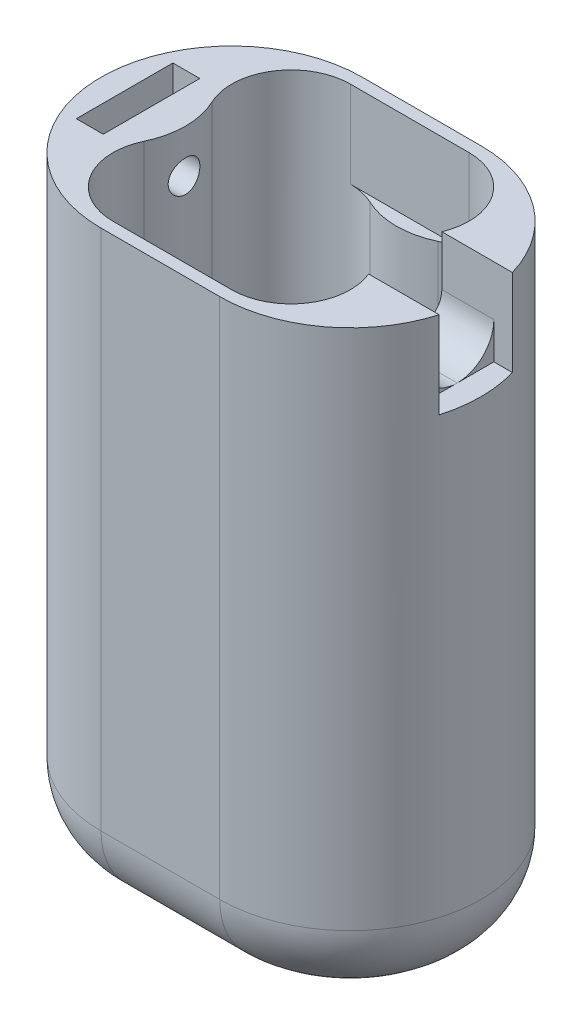
SolidWorks part; units mm, degrees
ref_plane "Front Plane" through (0, 0, 0) normal (0, 0, 1) x (1, 0, 0)
ref_plane "Top Plane" through (0, 0, 0) normal (0, 1, 0) x (1, 0, 0)
ref_plane "Right Plane" through (0, 0, 0) normal (1, 0, 0) x (0, 0, -1)
sketch "Sketch1" plane through (0, 0, 0) normal (0, 1, 0) x (1, 0, 0)
  line L0 (0, 0) -> (-23.105, 0) construction
  line L1 (-7.5, 0) -> (7.5, 0) construction
  line L2 (0, 13.7042) -> (0, -14.0987) construction
  line L3 (-7.5, 16.5) -> (7.5, 16.5)
  line L4 (-7.5, -16.5) -> (7.5, -16.5)
  line L5 (-7.5, 15) -> (-7.5, 16.5) construction
  arc A0 (-4.2857, 14.2763) -> (-14.2763, 4.2857) centre (-7.5, 7.5) ccw
  arc A1 (4.2857, 14.2763) -> (14.2763, 4.2857) centre (7.5, 7.5) cw
  arc A2 (4.2857, -14.2763) -> (14.2763, -4.2857) centre (7.5, -7.5) ccw
  arc A3 (-4.2857, -14.2763) -> (-14.2763, -4.2857) centre (-7.5, -7.5) cw
  arc A4 (14.2763, -4.2857) -> (14.2763, 4.2857) centre (23.3114, 0) cw
  arc A5 (-4.2857, -14.2763) -> (4.2857, -14.2763) centre (0, -23.3114) cw
  arc A6 (-14.2763, 4.2857) -> (-14.2763, -4.2857) centre (-23.3114, 0) cw
  arc A7 (-4.2857, 14.2763) -> (4.2857, 14.2763) centre (0, 23.3114) ccw
  arc A8 (-7.5, 16.5) -> (-7.5, -16.5) centre (-7.5, 0) ccw
  arc A9 (7.5, -16.5) -> (7.5, 16.5) centre (7.5, 0) ccw
  point P5 (0, 0)
  point P16 (7.5, 0)
  point P19 (0, -7.5)
  point P22 (-7.5, 0)
  point P25 (0, 7.5)
  point P32 (-7.5, 16.992)
  point P33 (-7.5, 15)
  point P36 (-8.7147, 14.901)
  point P37 (-7.5, 17.0404)
  dimension "D1" = 15
  dimension "D2" = 10
  dimension "D3" = 1.5
extrude "Boss-Extrude1" add sketch "Sketch1" along normal blind 55
sketch "Sketch2" plane through (0, 0, 0) normal (0, -1, 0) x (1, 0, 0)
  line L0 (-7.5, 0) -> (7.5, 0) construction
  line L1 (-7.5, 16.5) -> (7.5, 16.5)
  line L2 (-7.5, -16.5) -> (7.5, -16.5)
  line L3 (7.5, -16.5) -> (-7.5, -16.5) construction
  arc A0 (-7.5, 16.5) -> (-7.5, -16.5) centre (-7.5, 0) ccw
  arc A1 (7.5, -16.5) -> (7.5, 16.5) centre (7.5, 0) ccw
  arc A2 (-7.5, 16.5) -> (-7.5, -16.5) centre (-7.5, 0) ccw construction
  point P3 (0, 0)
extrude "Boss-Extrude2" add sketch "Sketch2" along normal blind 10
fillet "Fillet1" radius 10 4 edges at (24, -10, 0) (0, -10, -16.5) (-24, -10, 0) (0, -10, 16.5)
sketch "Sketch4" plane through (0, 55, 0) normal (0, 1, 0) x (1, 0, 0)
  line L0 (-7.5, -16.5) -> (7.5, -16.5) construction
  line L1 (-7.5, 16.5) -> (7.5, 16.5)
  line L2 (-7.5, -16.5) -> (7.5, -16.5)
  line L3 (24, 0) -> (24, 4.625) construction
  line L4 (14.4271, 4.625) -> (23.3385, 4.625)
  line L5 (7.5, 16.5) -> (-7.5, 16.5) construction
  line L6 (14.4271, -4.625) -> (23.3385, -4.625)
  line L7 (-7.5, 15) -> (7.5, 15)
  line L8 (-24, 0) -> (-21.0182, 0) construction
  line L9 (24, 0) -> (24, -4.625) construction
  line L10 (7.5, -15) -> (-7.5, -15)
  line L12 (-17.6182, 0) -> (-13.3114, 0) construction
  line L15 (-21.0182, 6.1) -> (-17.6182, 6.1)
  line L16 (-21.0182, 6.1) -> (-21.0182, -6.1)
  line L17 (-21.0182, -6.1) -> (-17.6182, -6.1)
  line L18 (-17.6182, 6.1) -> (-17.6182, -6.1)
  arc A0 (-7.5, 16.5) -> (-7.5, -16.5) centre (-7.5, 0) ccw construction
  arc A1 (7.5, -16.5) -> (23.3385, -4.625) centre (7.5, 0) ccw
  arc A3 (7.5, -15) -> (14.4271, -4.625) centre (7.5, -7.5) ccw
  arc A4 (-4.2857, 14.2763) -> (-14.2763, 4.2857) centre (-7.5, 7.5) ccw construction
  arc A5 (4.2857, -14.2763) -> (14.2763, -4.2857) centre (7.5, -7.5) ccw construction
  arc A6 (14.2763, 4.2857) -> (4.2857, 14.2763) centre (7.5, 7.5) ccw construction
  arc A7 (14.4271, 4.625) -> (7.5, 15) centre (7.5, 7.5) ccw
  arc A9 (-14.2763, -4.2857) -> (-4.2857, -14.2763) centre (-7.5, -7.5) ccw construction
  arc A10 (-14.2763, -4.2857) -> (-4.2857, -14.2763) centre (-7.5, -7.5) ccw construction
  arc A11 (4.2857, -14.2763) -> (14.2763, -4.2857) centre (7.5, -7.5) ccw construction
  arc A12 (23.3385, 4.625) -> (7.5, 16.5) centre (7.5, 0) ccw
  arc A13 (-14.2763, -4.2857) -> (-14.2763, 4.2857) centre (-23.3114, 0) ccw
  arc A14 (7.5, -16.5) -> (7.5, 16.5) centre (7.5, 0) ccw construction
  arc A15 (-14.2763, -4.2857) -> (-14.2763, 4.2857) centre (-23.3114, 0) ccw construction
  arc A16 (-7.5, 15) -> (-14.2763, 4.2857) centre (-7.5, 7.5) ccw
  arc A17 (-14.2763, -4.2857) -> (-7.5, -15) centre (-7.5, -7.5) ccw
  arc A18 (-7.5, 16.5) -> (-7.5, -16.5) centre (-7.5, 0) ccw
  point P3 (0, 0)
  point P55 (-23.3114, 4.959)
  point P62 (-14.8682, 6.1)
  point P63 (-22.831, 6.1)
  dimension "D1" = 9.25
  dimension "D2" = 12.2
  dimension "D3" = 3.4
  dimension "D4" = 2.75
  dimension "D5" = 1.8128
extrude "Boss-Extrude3" add sketch "Sketch4" along normal blind 10.95
fillet "Fillet3" radius 4.625 2 edges at (18.8828, 55, 4.625) (18.8828, 55, -4.625)
ref_plane "Plane1" through (24, 0, 0) normal (1, 0, 0) x (0, 0, -1)
sketch "Sketch5" plane through (24, 0, 0) normal (1, 0, 0) x (0, 0, -1)
  line L0 (4.625, 65.95) -> (4.625, 59.625) construction
  line L1 (-4.625, 65.95) -> (4.625, 65.95)
  line L2 (-4.625, 65.95) -> (-4.625, 55)
  line L3 (-4.625, 55) -> (4.625, 55)
  line L4 (4.625, 65.95) -> (4.625, 55)
extrude "Cut-Extrude1" cut sketch "Sketch5" against normal blind 3
sketch "Sketch6" plane through (0, 0, 0) normal (1, 0, 0) x (0, 0, -1)
  line L0 (-6.1, 65.95) -> (6.1, 55) construction
  circle A0 centre (0, 60.475) radius 2
  point P6 (0, 0)
  dimension "D1" = 4
extrude "Cut-Extrude2" cut sketch "Sketch6" against normal blind 23
